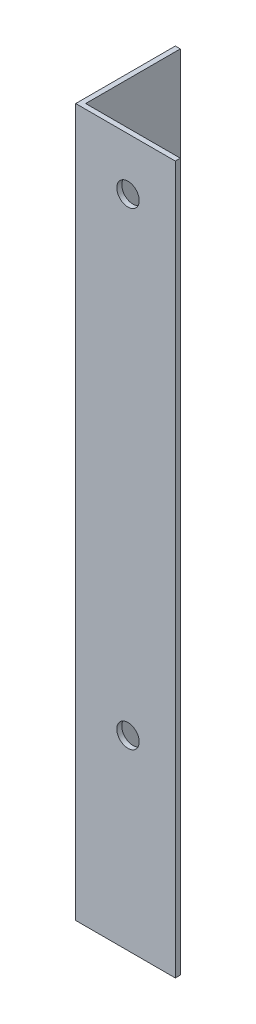
SolidWorks part; units mm, degrees
material "1060 Сплав"
ref_plane "Спереди" through (0, 0, 0) normal (0, 0, 1) x (1, 0, 0)
ref_plane "Сверху" through (0, 0, 0) normal (0, 1, 0) x (1, 0, 0)
ref_plane "Справа" through (0, 0, 0) normal (1, 0, 0) x (0, 0, -1)
sketch "Эскиз1" plane through (0, 0, 0) normal (0, 1, 0) x (1, 0, 0)
  line L0 (0, 0) -> (0, 20)
  line L1 (0, 20) -> (1, 20)
  line L2 (1, 20) -> (1, 1)
  line L3 (1, 1) -> (20, 1)
  line L4 (20, 1) -> (20, 0)
  line L5 (20, 0) -> (0, 0)
  dimension "D1" = 1
  dimension "D2" = 20
extrude "Бобышка-Вытянуть1" add sketch "Эскиз1" along normal blind 142
sketch "Эскиз2" plane through (0, 0, -1) normal (0, 0, -1) x (-1, 0, 0)
  line L0 (-10.5, 0) -> (-10.5, 142) construction
  line L1 (-20, 0) -> (-1, 0) construction
  line L2 (-20, 142) -> (-1, 142) construction
  circle A0 centre (-10.5, 131.5) radius 2.25
  dimension "D1" = 4.5
  dimension "D3" = 10.5
extrude "Вырез-Вытянуть1" cut sketch "Эскиз2" against normal through all
sketch "Эскиз3" plane through (0, 0, 0) normal (0, 0, 1) x (1, 0, 0)
  circle A0 centre (10.5, 37.4112) radius 2.25 construction
  circle A1 centre (10.5, 37.4112) radius 2.25
extrude "Вырез-Вытянуть2" cut sketch "Эскиз3" against normal through all
